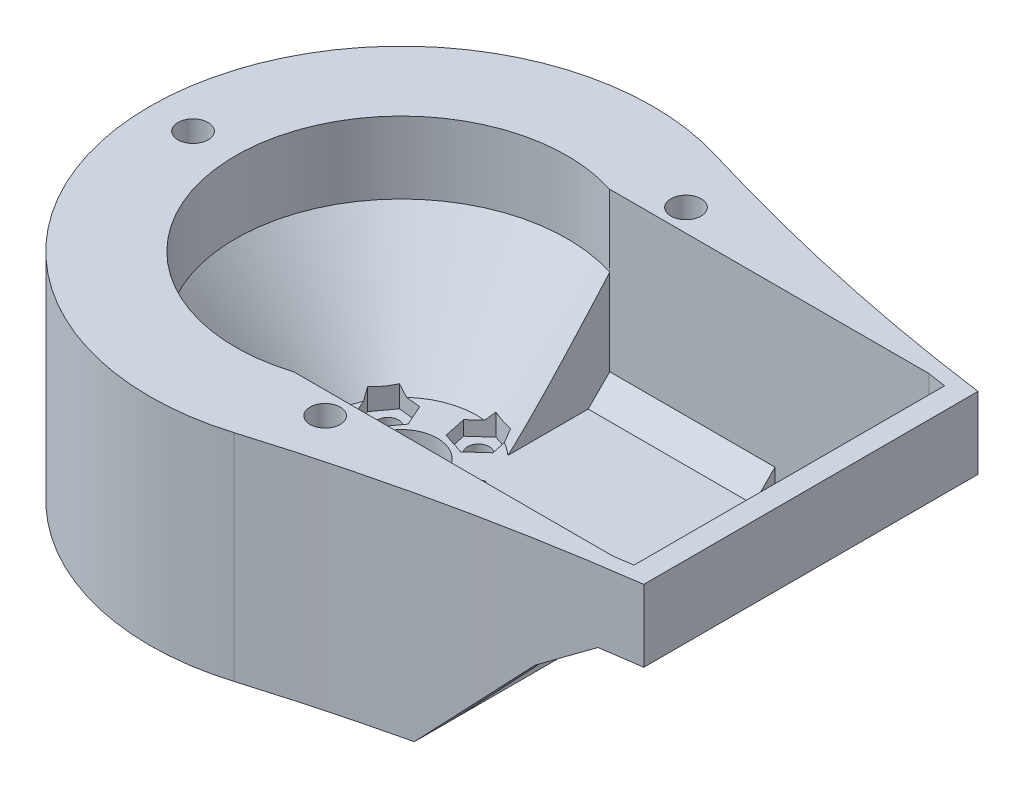
SolidWorks part; units mm, degrees
ref_plane "Front Plane" through (0, 0, 0) normal (0, 0, 1) x (1, 0, 0)
ref_plane "Top Plane" through (0, 0, 0) normal (0, 1, 0) x (1, 0, 0)
ref_plane "Right Plane" through (0, 0, 0) normal (1, 0, 0) x (0, 0, -1)
sketch "Sketch1" plane through (0, 0, 0) normal (0, 1, 0) x (1, 0, 0)
  line L0 (0, 0) -> (180, 0) construction
  arc A0 (10.1761, 33.488) -> (10.1761, -33.488) centre (0, 0) ccw
  arc A1 (172.264, -30.0192) -> (172.264, 30.0192) centre (180, 0) ccw
  arc A3 (10.1761, 33.488) -> (172.264, 30.0192) centre (97.4, 320.5281) ccw
  arc A4 (10.1761, -33.488) -> (172.264, -30.0192) centre (97.4, -320.5281) cw
  dimension "D1" = 70
  dimension "D3" = 62
  dimension "D4" = 300
  dimension "D5" = 300
  dimension "D2" = 180
extrude "Boss-Extrude1" add sketch "Sketch1" along normal blind 25 contours A1 A0 region at (84.3798, 0, 0)
sketch "Sketch18" plane through (0, 0, 0) normal (0, -1, 0) x (1, 0, 0)
  line L0 (0, 0) -> (29, 0) construction
  line L3 (8, -21) -> (50, -21) construction
  line L4 (8, -21) -> (8, 21) construction
  line L5 (8, 21) -> (50, 21) construction
  line L6 (50, -21) -> (50, 21) construction
  line L7 (8, -21) -> (50, 21) construction
  line L8 (8, 21) -> (50, -21) construction
  line L9 (44.5, 15.5) -> (44.5, -15.5) construction
  line L10 (13.5, -15.5) -> (44.5, -15.5) construction
  line L11 (13.5, 15.5) -> (13.5, -15.5) construction
  line L12 (13.5, 15.5) -> (44.5, 15.5) construction
  circle A1 centre (29, 0) radius 11.5
  circle A2 centre (13.5, 15.5) radius 1.6
  circle A3 centre (44.5, 15.5) radius 1.6
  circle A4 centre (44.5, -15.5) radius 1.6
  circle A5 centre (13.5, -15.5) radius 1.6
  point P0 (29, 0)
  dimension "D1" = 42
  dimension "D4" = 23
  dimension "D5" = 3.2
  dimension "D6" = 3.2
  dimension "D7" = 3.2
  dimension "D8" = 3.2
  dimension "D2" = 42
  dimension "D3" = 29
  dimension "D9" = 31
sketch "Sketch20" plane through (0, 0, 0) normal (0, 0, 1) x (1, 0, 0)
  line L0 (0, 0) -> (30, 0)
  line L1 (10.1761, 0) -> (172.264, 0) construction
  line L2 (30, 0) -> (65.7037, 25)
  line L3 (172.264, 25) -> (10.1761, 25) construction
  line L4 (8, 0) -> (50, 0) construction
  line L5 (65.7037, 25) -> (211, 25)
  line L6 (211, 25) -> (211, 0)
  line L7 (211, 0) -> (30, 0)
  dimension "D1" = 145
  dimension "D2" = 30
extrude "Cut-Extrude1" cut sketch "Sketch20" against normal mid plane 80 contours L7 L6 L5 L2 region at (129.1004, 12.0441, 0)
sketch "Sketch21" plane through (0, 0, 0) normal (0, -1, 0) x (1, 0, 0)
  line L0 (8, 21) -> (50, 21) construction
  line L1 (7, -22) -> (51, -22)
  line L2 (7, -22) -> (7, 22)
  line L3 (7, 22) -> (51, 22)
  line L4 (51, -22) -> (51, 22) construction
  line L5 (7, -22) -> (51, 22) construction
  line L6 (7, 22) -> (51, -22) construction
  line L7 (50, -21) -> (50, 21) construction
  line L9 (51, 22) -> (56, 22)
  line L10 (51, 22) -> (51, -22) construction
  line L11 (51, -22) -> (56, -22)
  line L12 (56, 22) -> (56, -22)
  point P0 (29, 0)
  dimension "D1" = 1
  dimension "D2" = 1
  dimension "D3" = 5
extrude "Cut-Extrude2" cut sketch "Sketch21" against normal through all
sketch "Sketch22" plane through (0, 0, 0) normal (0, -1, 0) x (1, 0, 0)
  line L8 (30, 28.1974) -> (30, -28.1974)
  arc A0 (10.1761, 33.488) -> (10.1761, -33.488) centre (0, 0) ccw
  arc A1 (30, -28.1974) -> (10.1761, -33.488) centre (97.4, -320.5281) ccw construction
  arc A2 (10.1761, 33.488) -> (30, 28.1974) centre (97.4, 320.5281) ccw construction
  arc A3 (30, -28.1974) -> (10.1761, -33.488) centre (97.4, -320.5281) ccw
  arc A4 (10.1761, 33.488) -> (30, 28.1974) centre (97.4, 320.5281) ccw
extrude "Boss-Extrude2" add sketch "Sketch22" along normal blind 5
sketch "Sketch23" plane through (0, -5, 0) normal (0, -1, 0) x (1, 0, 0)
  circle A0 centre (0, 0) radius 16
  dimension "D1" = 32
extrude "Boss-Extrude3" add sketch "Sketch23" along normal blind 5
sketch "Sketch24" plane through (0, -10, 0) normal (0, -1, 0) x (1, 0, 0)
  circle A0 centre (0, 0) radius 12.5
  dimension "D1" = 25
extrude "Boss-Extrude4" add sketch "Sketch24" along normal blind 6.5
sketch "Sketch25" plane through (0, -16.5, 0) normal (0, -1, 0) x (1, 0, 0)
  line L0 (0, 0) -> (8.5, 0) construction
  circle A0 centre (0, 0) radius 5
  circle A1 centre (8.5, 0) radius 1.5
  circle A2 centre (2.6266, -8.084) radius 1.5
  circle A3 centre (-6.8766, -4.9962) radius 1.5
  circle A4 centre (-6.8766, 4.9962) radius 1.5
  circle A5 centre (2.6266, 8.084) radius 1.5
  point P16 (0, 0)
  dimension "D1" = 10
  dimension "D2" = 3
  dimension "D3" = 8.5
extrude "Cut-Extrude6" cut sketch "Sketch25" against normal through all contours A0 | A5 | A4 | A3 | A2 | A1 region at (0, -16.5, 0) region at (8.5, -16.5, 0) region at (2.6266, -16.5, -8.084) region at (-6.8766, -16.5, -4.9962) region at (-6.8766, -16.5, 4.9962) region at (2.6266, -16.5, 8.084)
sketch "Sketch28" plane through (0, 25, 0) normal (0, 1, 0) x (1, 0, 0)
  circle A0 centre (0, 0) radius 23.0868
extrude "Cut-Extrude9" cut sketch "Sketch28" against normal blind 10
sketch "Sketch29" plane through (0, 15, 0) normal (0, 1, 0) x (1, 0, 0)
  circle A0 centre (0, 0) radius 23.0868
extrude "Cut-Extrude10" cut sketch "Sketch29" against normal blind 15 draft 40
chamfer "Chamfer1" distance 5 distance2 17 2 edges at (30, 0, 25.0987) (30, 0, -25.0987) first distance on face at (30, -1.6667, 0)
sketch "Sketch27" plane through (0, 0, 0) normal (0, 0, 1) x (1, 0, 0)
  line L0 (43.9256, 9.7508) -> (65.7037, 25) construction
  line L1 (65.7037, 25) -> (51.4222, 25)
  line L4 (51.4222, 25) -> (51.4222, 15)
  line L5 (51.4222, 15) -> (65.7037, 25)
  dimension "D1" = 10
extrude "Cut-Extrude8" cut sketch "Sketch27" against normal mid plane 56.5
chamfer "Chamfer2" distance 3 angle 45 2 edges at (18.5, 0, 22) (18.5, 0, -22)
sketch "Sketch30" plane through (0, 25, 0) normal (0, 1, 0) x (1, 0, 0)
  line L0 (7, 7.8266) -> (7, 19) construction
  line L1 (54, 21.6144) -> (54, -21.6144)
  line L3 (51.4222, -24.0723) -> (51.4222, -22)
  line L5 (51.4222, 22) -> (51.4222, 24.0723)
  line L6 (57, 23.2608) -> (57, -23.6839)
  line L7 (57, 23.6839) -> (57, -23.6839) construction
  line L8 (54, 23.6839) -> (54, -23.6839) construction
  arc A0 (10.1761, 33.488) -> (51.4222, 24.0723) centre (97.4, 320.5281) ccw construction
  arc A1 (51.4222, 24.0723) -> (57, 23.2608) centre (97.4, 320.5281) ccw
  arc A2 (51.4222, -24.0723) -> (10.1761, -33.488) centre (97.4, -320.5281) ccw construction
  arc A3 (57, -23.2608) -> (51.4222, -24.0723) centre (97.4, -320.5281) ccw
  arc A4 (51.4222, 22) -> (54, 21.6144) centre (97.4, 320.5281) ccw
  arc A5 (51.4222, -22) -> (54, -21.6144) centre (97.4, -320.5281) cw
  line M3 (51.4222, 22) -> (51.4222, 24.0723)
  line M7 (51.4222, -24.0723) -> (51.4222, -22)
  dimension "D1" = 47
  dimension "D2" = 3
extrude "Boss-Extrude5" add sketch "Sketch30" against normal up to vertex (10 mm away) contours A5 A3 L6 A1 A4 L1 M7 M3 region at (55.2992, 25, 0) up to point (51.4222, 15, -24.0723)
sketch "Sketch31" plane through (0, 25, 0) normal (0, 1, 0) x (1, 0, 0)
  line L0 (0, 0) -> (-29, 0) construction
  circle A0 centre (-29, 0) radius 2.1
  circle A1 centre (14.5, 25.1147) radius 2.1
  circle A2 centre (14.5, -25.1147) radius 2.1
  point P11 (0, 0)
  dimension "D1" = 4.2
  dimension "D2" = 29
extrude "Cut-Extrude11" cut sketch "Sketch31" against normal through all
sketch "Sketch32" plane through (0, -5, 0) normal (0, -1, 0) x (1, 0, 0)
  circle A0 centre (-29, 0) radius 4
  circle A1 centre (14.5, 25.1147) radius 4
  circle A2 centre (14.5, -25.1147) radius 4
  dimension "D1" = 8
  dimension "D2" = 8
  dimension "D3" = 8
extrude "Cut-Extrude12" cut sketch "Sketch32" against normal blind 5
sketch "Sketch33" plane through (0, 0, 0) normal (0, 1, 0) x (1, 0, 0)
  line L0 (5.6467, -7.1027) -> (3.2869, -4.9779)
  line L1 (8.5, 3.1754) -> (5.75, 1.5877)
  line L2 (5.75, 1.5877) -> (5.75, -1.5877)
  line L3 (5.75, -1.5877) -> (8.5, -3.1754)
  line L4 (8.5, -3.1754) -> (11.25, -1.5877)
  line L5 (11.25, -1.5877) -> (11.25, 1.5877)
  line L6 (11.25, 1.5877) -> (8.5, 3.1754)
  line L7 (3.2869, -4.9779) -> (0.2668, -5.9592)
  line L8 (0.2668, -5.9592) -> (-0.3934, -9.0652)
  line L9 (-0.3934, -9.0652) -> (1.9664, -11.19)
  line L10 (1.9664, -11.19) -> (4.9864, -10.2088)
  line L11 (4.9864, -10.2088) -> (5.6467, -7.1027)
  line L12 (-5.0102, -7.5651) -> (-3.7186, -4.6643)
  line L13 (-3.7186, -4.6643) -> (-5.5851, -2.0953)
  line L14 (-5.5851, -2.0953) -> (-8.7431, -2.4272)
  line L15 (-8.7431, -2.4272) -> (-10.0347, -5.3281)
  line L16 (-10.0347, -5.3281) -> (-8.1682, -7.8971)
  line L17 (-8.1682, -7.8971) -> (-5.0102, -7.5651)
  line L18 (-8.7431, 2.4272) -> (-5.5851, 2.0953)
  line L19 (-5.5851, 2.0953) -> (-3.7186, 4.6643)
  line L20 (-3.7186, 4.6643) -> (-5.0102, 7.5651)
  line L21 (-5.0102, 7.5651) -> (-8.1682, 7.8971)
  line L22 (-8.1682, 7.8971) -> (-10.0347, 5.3281)
  line L23 (-10.0347, 5.3281) -> (-8.7431, 2.4272)
  line L24 (-0.3934, 9.0652) -> (0.2668, 5.9592)
  line L25 (0.2668, 5.9592) -> (3.2869, 4.9779)
  line L26 (3.2869, 4.9779) -> (5.6467, 7.1027)
  line L27 (5.6467, 7.1027) -> (4.9864, 10.2088)
  line L28 (4.9864, 10.2088) -> (1.9664, 11.19)
  line L29 (1.9664, 11.19) -> (-0.3934, 9.0652)
  circle A0 centre (8.5, 0) radius 2.75 construction
  circle A1 centre (2.6266, -8.084) radius 2.75 construction
  circle A2 centre (-6.8766, -4.9962) radius 2.75 construction
  circle A3 centre (-6.8766, 4.9962) radius 2.75 construction
  circle A4 centre (2.6266, 8.084) radius 2.75 construction
  point P44 (0, 0)
  dimension "D1" = 5.5
extrude "Cut-Extrude13" cut sketch "Sketch33" against normal blind 2 and the other way blind 15
